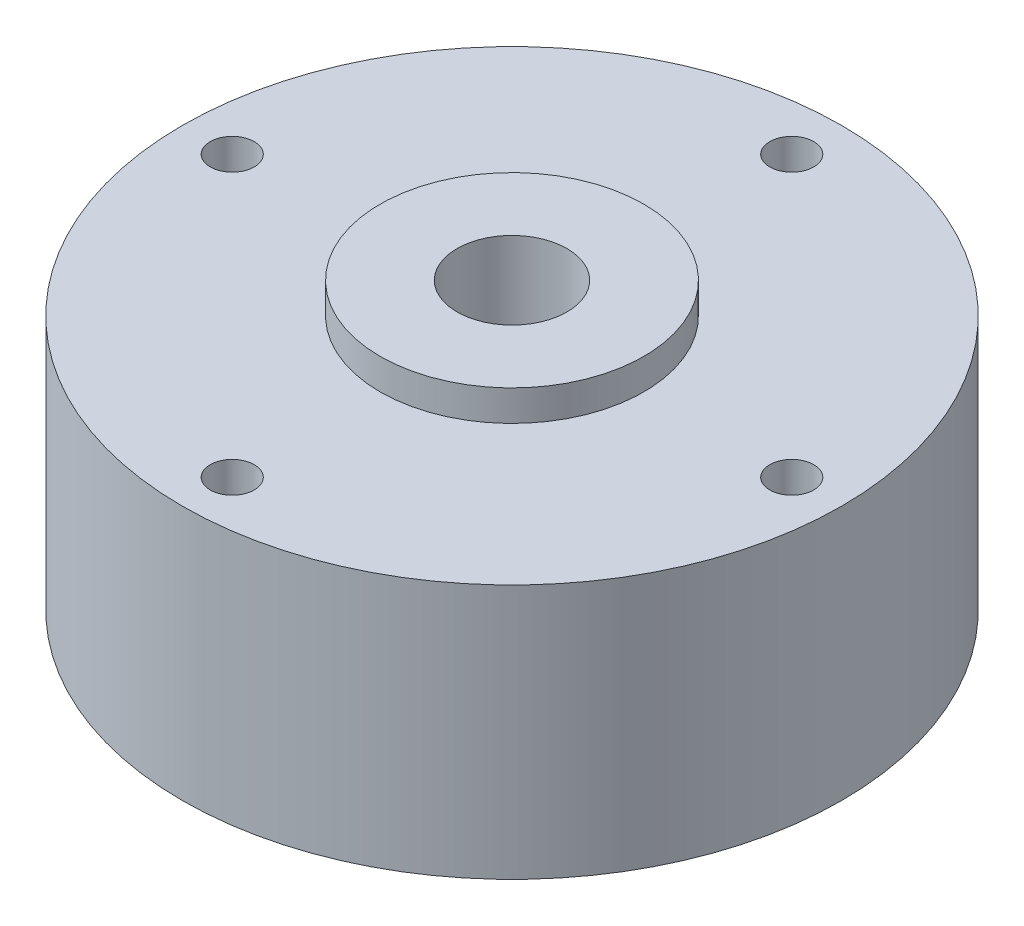
SolidWorks part; units mm, degrees
ref_plane "Front plane" through (0, 0, 0) normal (0, 0, 1) x (1, 0, 0)
ref_plane "Top plane" through (0, 0, 0) normal (0, 1, 0) x (1, 0, 0)
ref_plane "Right plane" through (0, 0, 0) normal (1, 0, 0) x (0, 0, -1)
ref_axis "Axis X" through (0, 0, 0) along (1, 0, 0)
ref_axis "Axis Y" through (0, 0, 0) along (0, 1, 0)
ref_axis "Axis Z" through (0, 0, 0) along (0, 0, 1)
sketch "Sketch1" plane through (0, 0, 0) normal (0, 1, 0) x (1, 0, 0)
  circle A0 centre (0, 0) radius 15
  dimension "D1" = 30
extrude "Extrude1" add sketch "Sketch1" along normal blind 13
sketch "Sketch2" plane through (0, 13, 0) normal (0, 1, 0) x (1, 0, 0)
  circle A0 centre (0, 0) radius 6
  circle A1 centre (0, 0) radius 15
  dimension "D1" = 30
  dimension "D2" = 12
extrude "Extrude2" cut sketch "Sketch2" against normal blind 1.4
sketch "Sketch3" plane through (0, 13, 0) normal (0, 1, 0) x (1, 0, 0)
  line L0 (0, 0) -> (0, 12.7279) construction
  circle A0 centre (0, 0) radius 12.7279 construction
  circle A1 centre (0, 12.7279) radius 1
  circle A2 centre (12.7279, 0) radius 1
  circle A3 centre (0, -12.7279) radius 1
  circle A4 centre (-12.7279, 0) radius 1
  dimension "D1" = 25.4558
  dimension "D2" = 2
extrude "Extrude3" cut sketch "Sketch3" against normal blind 4.4
sketch "Sketch4" plane through (0, 0, 0) normal (0, -1, 0) x (1, 0, 0)
  line L0 (0, 0) -> (0, 5) construction
  circle A0 centre (0, 0) radius 5 construction
  circle A1 centre (0, 5) radius 1
  circle A2 centre (5, 0) radius 1
  circle A3 centre (0, -5) radius 1
  circle A4 centre (-5, 0) radius 1
  dimension "D1" = 2
  dimension "D3" = 10
  dimension "D2" = 4
extrude "Extrude4" [suppressed] cut sketch "Sketch4" against normal blind 3
sketch "Sketch5" plane through (0, 0, 0) normal (0, -1, 0) x (1, 0, 0)
  line L1 (-11, 5) -> (11, 5) construction
  line L2 (-11, 5) -> (-11, -5) construction
  line L3 (-11, -5) -> (11, -5) construction
  line L4 (11, 5) -> (11, -5) construction
  line L5 (-11, 5) -> (11, -5) construction
  line L6 (-11, -5) -> (11, 5) construction
  circle A0 centre (-11, 5) radius 1
  circle A1 centre (11, 5) radius 1
  circle A2 centre (11, -5) radius 1
  circle A3 centre (-11, -5) radius 1
  point P0 (0, 0)
  dimension "D2" = 2
  dimension "D1" = 2
  dimension "D3" = 2
  dimension "D4" = 2
  dimension "D5" = 22
  dimension "D6" = 10
extrude "Extrude5" cut sketch "Sketch5" against normal blind 3
chamfer "Chamfer1" [suppressed] distance 0.5 angle 45
sketch "Sketch6" plane through (0, 0, 0) normal (0, -1, 0) x (1, 0, 0)
  circle A0 centre (0, 0) radius 2.5
  dimension "D1" = 5
extrude "Extrude6" cut sketch "Sketch6" against normal through all
equation "\"motor_D\"= 30'Motor diameter"
equation "\"motor_H\"= 13'Motor heigh"
equation "\"motor_d1\"= 25.4558'Seating diameter of screws on the fixed part of the motor"
equation "\"motor_s1\"= 2'Screws diameter on the fixed part of motor"
equation "\"motor_d2\"= 0'Seating diameter of screws on the moving part of the motor (if this parameter is not determine, write 0)"
equation "\"motor_s2\"= 2'Screws diameter on the moving part of motor"
equation "\"motor_Dc\"= 5'Central hole diameter of motor"
equation "\"bearing_d1\"= 6'Bearing inner diameter"
equation "\"bearing_d2\"= 17'Bearing external diameter"
equation "\"bearing h\"= 6'Bearing heigh"
equation "\"pin_d\"= 2'Pin diameter"
equation "\"pin_h\"= 12'Pin heigh"
equation "\"magnet_d1\"= 5'Magnet inner diameter"
equation "\"magnet_d2\"= 9.5'Magnet external diameter"
equation "\"magnet_h\"= 3'Magnet heigh"
equation "\"motor_a2\"= 10'Seating parameter in rectangle of screws on the moving part of the motor"
equation "\"motor_b2\"= 22'Seating parameter in rectangle of screws on the moving part of the motor"
equation "\"D1@Sketch1\"=\"motor_D\""
equation "\"D1@Extrude1\"=\"motor_H\""
equation "\"D1@Sketch2\"=\"motor_D\""
equation "\"motor_cmd\"= 12'Central magnet mount diameter"
equation "\"motor_cmh\"= 1.4'Central magnet mount heigh (if not write 0)"
equation "\"D2@Sketch2\"=\"motor_cmd\""
equation "\"D1@Extrude2\"= \"motor_cmh\""
equation "\"Extrude2\"= IIF ( \"motor_cmh\" = 0 , \"suppressed\" , \"unsuppressed\" )"
equation "\"D1@Sketch3\"=\"motor_d1\""
equation "\"D2@Sketch3\"=\"motor_s1\""
equation "\"D1@Extrude3\"=\"motor_cmh\"+3"
equation "\"D1@Sketch4\"=\"motor_s2\""
equation "\"D3@Sketch4\"=if( \"motor_d2\"=0,10,\"motor_d2\")"
equation "\"Extrude4\"= IIF ( \"motor_d2\" = 0 , \"suppressed\" , \"unsuppressed\" )"
equation "\"D1@Sketch5\"=\"motor_s2\""
equation "\"D2@Sketch5\"=\"D1@Sketch5\""
equation "\"D3@Sketch5\"=\"D2@Sketch5\""
equation "\"D4@Sketch5\"=\"D2@Sketch5\""
equation "\"D5@Sketch5\"=\"motor_b2\""
equation "\"D6@Sketch5\"=\"motor_a2\""
equation "\"Extrude5\"= IIF ( \"motor_d2\" = 0 , \"unsuppressed\" , \"suppressed\" )"
equation "\"D1@Sketch6\"=\"motor_Dc\""
equation "\"motor_whR\"= 10'Distance from center of motor to wires"
equation "\"print_offset\"= 0.2'Offset for printing holes"
equation "\"ft_sensor_d1\"= 9.8"
equation "\"ft_sensor_d2\"= 24.9"
equation "\"ft_sensor_d3\"= 22.6'Inner diameter of "
equation "\"ft_sensor_h\"= 7.1"
equation "\"ft_sensor_whD\" = 5"
